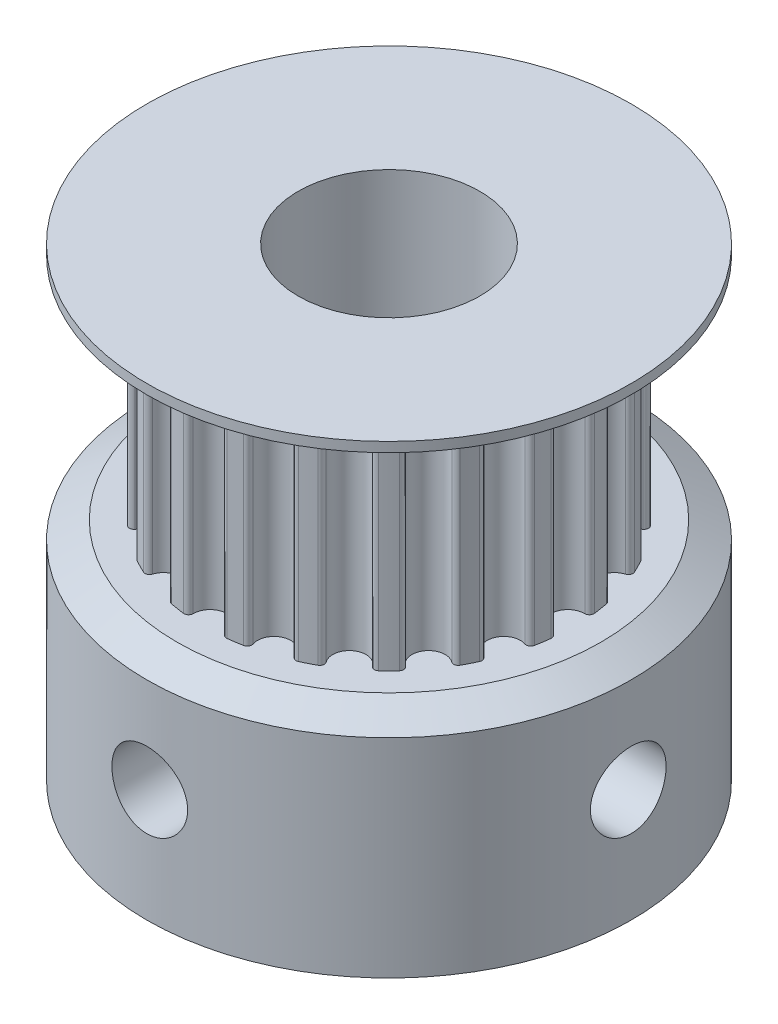
SolidWorks part; units mm, degrees
note: '?' marks a value the reader was unsure of.
material "1060 Alloy"
ref_plane "Спереди" through (0, 0, 0) normal (0, 0, 1) x (1, 0, 0)
ref_plane "Сверху" through (0, 0, 0) normal (0, 1, 0) x (1, 0, 0)
ref_plane "Справа" through (0, 0, 0) normal (1, 0, 0) x (0, 0, -1)
other "Configuration Table"
sketch "Эскиз1" plane through (0, 0, 0) normal (0, 1, 0) x (1, 0, 0)
  circle A0 centre (0, 0) radius 8
  circle A1 centre (0, 0) radius 3
  dimension "D1" = 16
  dimension "D2" = 6
extrude "Бобышка-Вытянуть1" add sketch "Эскиз1" along normal blind 7.45
sketch "Эскиз2" plane through (0, 7.45, 0) normal (0, 1, 0) x (1, 0, 0)
  arc A0 (-2.5575, 5.549) -> (-2.986, 5.3307) centre (0, 0) ccw
  circle A1 centre (0, 0) radius 3 construction
  circle A2 centre (0, 0) radius 3
  arc A3 (-0.55, 5.9169) -> (0.55, 5.9169) centre (0, 5.91) ccw
  arc A4 (1.3054, 5.7972) -> (2.3515, 5.4573) centre (1.8263, 5.6207) ccw
  arc A5 (3.0329, 5.1101) -> (3.9228, 4.4636) centre (3.4738, 4.7813) ccw
  arc A6 (4.4636, 3.9228) -> (5.1101, 3.0329) centre (4.7813, 3.4738) ccw
  arc A7 (5.4573, 2.3515) -> (5.7972, 1.3054) centre (5.6207, 1.8263) ccw
  arc A8 (5.9169, 0.55) -> (5.9169, -0.55) centre (5.91, 0) ccw
  arc A9 (5.7972, -1.3054) -> (5.4573, -2.3515) centre (5.6207, -1.8263) ccw
  arc A10 (5.1101, -3.0329) -> (4.4636, -3.9228) centre (4.7813, -3.4738) ccw
  arc A11 (3.9228, -4.4636) -> (3.0329, -5.1101) centre (3.4738, -4.7813) ccw
  arc A12 (2.3515, -5.4573) -> (1.3054, -5.7972) centre (1.8263, -5.6207) ccw
  arc A13 (0.55, -5.9169) -> (-0.55, -5.9169) centre (0, -5.91) ccw
  arc A14 (-1.3054, -5.7972) -> (-2.3515, -5.4573) centre (-1.8263, -5.6207) ccw
  arc A15 (-3.0329, -5.1101) -> (-3.9228, -4.4636) centre (-3.4738, -4.7813) ccw
  arc A16 (-4.4636, -3.9228) -> (-5.1101, -3.0329) centre (-4.7813, -3.4738) ccw
  arc A17 (-5.4573, -2.3515) -> (-5.7972, -1.3054) centre (-5.6207, -1.8263) ccw
  arc A18 (-5.9169, -0.55) -> (-5.9169, 0.55) centre (-5.91, 0) ccw
  arc A19 (-5.7972, 1.3054) -> (-5.4573, 2.3515) centre (-5.6207, 1.8263) ccw
  arc A20 (-5.1101, 3.0329) -> (-4.4636, 3.9228) centre (-4.7813, 3.4738) ccw
  arc A21 (-3.9228, 4.4636) -> (-3.0329, 5.1101) centre (-3.4738, 4.7813) ccw
  arc A22 (-2.3515, 5.4573) -> (-1.3054, 5.7972) centre (-1.8263, 5.6207) ccw
  arc A23 (-4.147, 4.4871) -> (-4.4871, 4.147) centre (0, 0) ccw
  arc A24 (-0.7176, 6.0677) -> (-1.1926, 5.9925) centre (0, 0) ccw
  arc A25 (1.1926, 5.9925) -> (0.7176, 6.0677) centre (0, 0) ccw
  arc A26 (2.986, 5.3307) -> (2.5575, 5.549) centre (0, 0) ccw
  arc A27 (4.4871, 4.147) -> (4.147, 4.4871) centre (0, 0) ccw
  arc A28 (5.549, 2.5575) -> (5.3307, 2.986) centre (0, 0) ccw
  arc A29 (6.0677, 0.7176) -> (5.9925, 1.1926) centre (0, 0) ccw
  arc A30 (-5.3307, 2.986) -> (-5.549, 2.5575) centre (0, 0) ccw
  arc A31 (-5.9925, 1.1926) -> (-6.0677, 0.7176) centre (0, 0) ccw
  arc A32 (-6.0677, -0.7176) -> (-5.9925, -1.1926) centre (0, 0) ccw
  arc A33 (-5.549, -2.5575) -> (-5.3307, -2.986) centre (0, 0) ccw
  arc A34 (-4.4871, -4.147) -> (-4.147, -4.4871) centre (0, 0) ccw
  arc A35 (-2.986, -5.3307) -> (-2.5575, -5.549) centre (0, 0) ccw
  arc A36 (5.9925, -1.1926) -> (6.0677, -0.7176) centre (0, 0) ccw
  arc A37 (5.3307, -2.986) -> (5.549, -2.5575) centre (0, 0) ccw
  arc A38 (4.147, -4.4871) -> (4.4871, -4.147) centre (0, 0) ccw
  arc A39 (2.5575, -5.549) -> (2.986, -5.3307) centre (0, 0) ccw
  arc A40 (0.7176, -6.0677) -> (1.1926, -5.9925) centre (0, 0) ccw
  arc A41 (-1.1926, -5.9925) -> (-0.7176, -6.0677) centre (0, 0) ccw
  arc A42 (5.9169, 0.55) -> (6.0677, 0.7176) centre (5.9188, 0.6999) ccw
  arc A43 (5.7972, 1.3054) -> (5.9925, 1.1926) centre (5.8454, 1.1633) cw
  arc A44 (5.4573, 2.3515) -> (5.549, 2.5575) centre (5.4128, 2.4947) ccw
  arc A45 (5.1101, 3.0329) -> (5.3307, 2.986) centre (5.1998, 2.9127) cw
  arc A46 (5.1101, -3.0329) -> (5.3307, -2.986) centre (5.1998, -2.9127) ccw
  arc A47 (5.4573, -2.3515) -> (5.549, -2.5575) centre (5.4128, -2.4947) cw
  arc A48 (5.7972, -1.3054) -> (5.9925, -1.1926) centre (5.8454, -1.1633) ccw
  arc A49 (5.9169, -0.55) -> (6.0677, -0.7176) centre (5.9188, -0.6999) cw
  arc A50 (3.9228, -4.4636) -> (4.147, -4.4871) centre (4.0452, -4.377) ccw
  arc A51 (4.4636, -3.9228) -> (4.4871, -4.147) centre (4.377, -4.0452) cw
  arc A52 (3.0329, -5.1101) -> (2.986, -5.3307) centre (2.9127, -5.1998) cw
  arc A53 (1.3054, -5.7972) -> (1.1926, -5.9925) centre (1.1633, -5.8454) cw
  arc A54 (0.55, -5.9169) -> (0.7176, -6.0677) centre (0.6999, -5.9188) ccw
  arc A55 (-0.55, -5.9169) -> (-0.7176, -6.0677) centre (-0.6999, -5.9188) cw
  arc A56 (-1.3054, -5.7972) -> (-1.1926, -5.9925) centre (-1.1633, -5.8454) ccw
  arc A57 (-2.3515, -5.4573) -> (-2.5575, -5.549) centre (-2.4947, -5.4128) cw
  arc A58 (-3.0329, -5.1101) -> (-2.986, -5.3307) centre (-2.9127, -5.1998) ccw
  arc A59 (-3.9228, -4.4636) -> (-4.147, -4.4871) centre (-4.0452, -4.377) cw
  arc A60 (-4.4636, -3.9228) -> (-4.4871, -4.147) centre (-4.377, -4.0452) ccw
  arc A61 (-5.9169, -0.55) -> (-6.0677, -0.7176) centre (-5.9188, -0.6999) ccw
  arc A62 (-5.7972, -1.3054) -> (-5.9925, -1.1926) centre (-5.8454, -1.1633) cw
  arc A63 (-5.4573, -2.3515) -> (-5.549, -2.5575) centre (-5.4128, -2.4947) ccw
  arc A64 (-5.1101, -3.0329) -> (-5.3307, -2.986) centre (-5.1998, -2.9127) cw
  arc A65 (-5.1101, 3.0329) -> (-5.3307, 2.986) centre (-5.1998, 2.9127) ccw
  arc A66 (-5.4573, 2.3515) -> (-5.549, 2.5575) centre (-5.4128, 2.4947) cw
  arc A67 (-5.7972, 1.3054) -> (-5.9925, 1.1926) centre (-5.8454, 1.1633) ccw
  arc A68 (-5.9169, 0.55) -> (-6.0677, 0.7176) centre (-5.9188, 0.6999) cw
  arc A69 (-4.4636, 3.9228) -> (-4.4871, 4.147) centre (-4.377, 4.0452) cw
  arc A70 (-3.9228, 4.4636) -> (-4.147, 4.4871) centre (-4.0452, 4.377) ccw
  arc A71 (-3.0329, 5.1101) -> (-2.986, 5.3307) centre (-2.9127, 5.1998) cw
  arc A72 (-2.3515, 5.4573) -> (-2.5575, 5.549) centre (-2.4947, 5.4128) ccw
  arc A73 (-1.3054, 5.7972) -> (-1.1926, 5.9925) centre (-1.1633, 5.8454) cw
  arc A74 (-0.55, 5.9169) -> (-0.7176, 6.0677) centre (-0.6999, 5.9188) ccw
  arc A75 (4.4636, 3.9228) -> (4.4871, 4.147) centre (4.377, 4.0452) ccw
  arc A76 (3.9228, 4.4636) -> (4.147, 4.4871) centre (4.0452, 4.377) cw
  arc A77 (0.55, 5.9169) -> (0.7176, 6.0677) centre (0.6999, 5.9188) cw
  arc A78 (1.3054, 5.7972) -> (1.1926, 5.9925) centre (1.1633, 5.8454) ccw
  arc A79 (3.0329, 5.1101) -> (2.986, 5.3307) centre (2.9127, 5.1998) ccw
  arc A80 (2.3515, 5.4573) -> (2.5575, 5.549) centre (2.4947, 5.4128) cw
  arc A81 (2.3515, -5.4573) -> (2.5575, -5.549) centre (2.4947, -5.4128) ccw
  point P69 (0, 0)
  point P135 (-0.5205, 6.0878)
  point P142 (0.5205, 6.0878)
  dimension "D1" = 12.22
  dimension "D2" = 1.1
  dimension "D3" = 0.75
  dimension "D5" = 0.15
  dimension "D6" = 0.15
  dimension "D4" = 20
extrude "Бобышка-Вытянуть2" add sketch "Эскиз2" along normal blind 7
sketch "Эскиз3" plane through (0, 14.45, 0) normal (0, 1, 0) x (1, 0, 0)
  circle A0 centre (0, 0) radius 3 construction
  circle A1 centre (0, 0) radius 3
  circle A2 centre (0, 0) radius 8 construction
  circle A3 centre (0, 0) radius 8
extrude "Бобышка-Вытянуть3" add sketch "Эскиз3" along normal blind 1.55
sketch "Эскиз4" plane through (0, 0, 0) normal (0, 0, 1) x (1, 0, 0)
  line L0 (-8, 3.725) -> (8, 3.725) construction
  line L1 (-8, 7.45) -> (-8, 0) construction
  line L2 (8, 0) -> (8, 7.45) construction
  circle A0 centre (0, 3.725) radius 1.25
  dimension "D1" = 2.5
extrude "Вырез-Вытянуть1" cut sketch "Эскиз4" along normal up to surface (7.9017 mm away)
sketch "Эскиз5" plane through (0, 0, 0) normal (1, 0, 0) x (0, 0, -1)
  line L0 (8, 3.725) -> (-7.9017, 3.725) construction
  line L1 (8, 0) -> (8, 7.45) construction
  circle A0 centre (0, 3.725) radius 1.25
  spline S1 degree 2 poles (-8, 4.975) (-7.8047, 3.725) (-8, 2.475) knots 0 0 0 1 1 1 weights 0.00675 0.008 0.00925 construction
  dimension "D1" = 2.5
extrude "Вырез-Вытянуть2" cut sketch "Эскиз5" along normal up to surface (7.9017 mm away)
sketch "Минимальный радиус ремня" plane through (0, 7.45, 0) normal (0, 1, 0) x (1, 0, 0)
  circle A0 centre (0, 0) radius 5.36
  arc A2 (-2.986, -5.3307) -> (-2.5575, -5.549) centre (0, 0) ccw construction
  dimension "D1" = 0.75
  dimension "D2" = 10.72
chamfer "Фаска1" distance 1 angle 30 2 edges at (0, 14.45, 8) (0, 7.45, 8)
ref_axis "Ось1" through (0, 16, 0) along (0, -1, 0)?
sketch "Sketch1" plane through (0, 16, 0) normal (0, 1, 0) x (1, 0, 0)
  circle A0 centre (0, 0) radius 8
  circle A1 centre (0, 0) radius 8 construction
extrude "Cut-Extrude1" cut sketch "Sketch1" against normal blind 0.65
